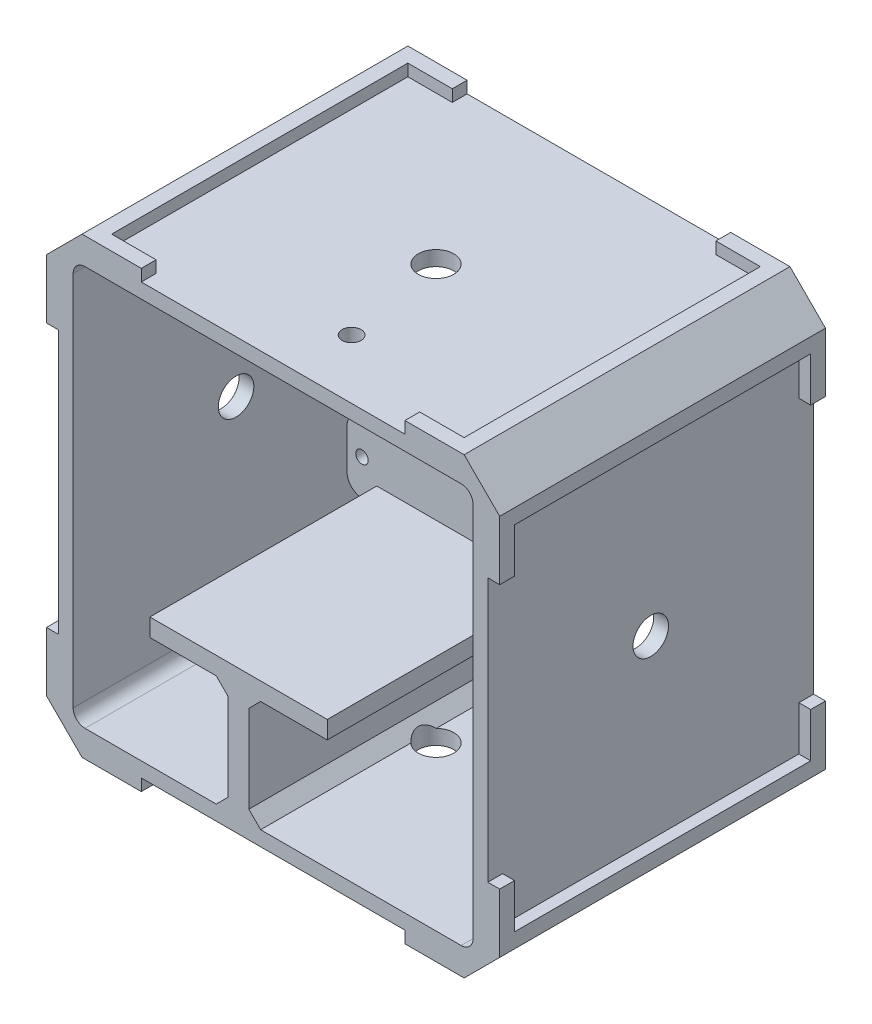
SolidWorks part; units mm, degrees
ref_plane "Front Plane" through (0, 0, 0) normal (0, 0, 1) x (1, 0, 0)
ref_plane "Top Plane" through (0, 0, 0) normal (0, 1, 0) x (1, 0, 0)
ref_plane "Right Plane" through (0, 0, 0) normal (1, 0, 0) x (0, 0, -1)
sketch "Sketch1" plane through (0, 0, 0) normal (0, 0, 1) x (1, 0, 0)
  line L0 (-33.75, -33.75) -> (33.75, -33.75) construction
  line L1 (-31.75, 33.75) -> (31.75, 33.75)
  line L2 (-33.75, 31.75) -> (-33.75, -31.75)
  line L3 (-31.75, -33.75) -> (31.75, -33.75)
  line L4 (33.75, 31.75) -> (33.75, -31.75)
  line L5 (-36.25, 32.25) -> (-36.25, -32.25)
  line L6 (33.75, 33.75) -> (33.75, -33.75) construction
  line L7 (-32.25, -36.25) -> (32.25, -36.25)
  line L8 (36.25, 32.25) -> (36.25, -32.25)
  line L9 (-32.25, 36.25) -> (32.25, 36.25)
  line L10 (-36.25, 36.25) -> (-36.25, -36.25) construction
  line L11 (-36.25, 36.25) -> (36.25, 36.25) construction
  line L12 (-33.75, 33.75) -> (33.75, 33.75) construction
  line L13 (-33.75, 33.75) -> (-33.75, -33.75) construction
  line L14 (-36.25, -36.25) -> (36.25, -36.25) construction
  line L15 (36.25, 36.25) -> (36.25, -36.25) construction
  line L16 (55, 0) -> (-55, 0) construction
  line L17 (0, -55) -> (0, 55) construction
  arc A0 (-36.25, 32.25) -> (-32.25, 36.25) centre (-32.25, 32.25) cw
  arc A1 (-31.75, 33.75) -> (-33.75, 31.75) centre (-31.75, 31.75) ccw
  arc A2 (-33.75, -31.75) -> (-31.75, -33.75) centre (-31.75, -31.75) ccw
  arc A3 (31.75, -33.75) -> (33.75, -31.75) centre (31.75, -31.75) ccw
  arc A4 (31.75, 33.75) -> (33.75, 31.75) centre (31.75, 31.75) cw
  arc A5 (-36.25, -32.25) -> (-32.25, -36.25) centre (-32.25, -32.25) ccw
  arc A6 (32.25, -36.25) -> (36.25, -32.25) centre (32.25, -32.25) ccw
  arc A7 (36.25, 32.25) -> (32.25, 36.25) centre (32.25, 32.25) ccw
  point P36 (-33.75, 0)
  point P39 (0, 33.75)
  dimension "D3" = 4
  dimension "D4" = 2
  dimension "D5" = 2
  dimension "D6" = 4
  dimension "D1" = 67.5
  dimension "D2" = 2.5
extrude "Boss-Extrude1" add sketch "Sketch1" along normal blind 55
sketch "Sketch2" plane through (0, 0, 0) normal (0, 0, 1) x (1, 0, 0)
  line L1 (-33.75, 33.75) -> (33.75, 33.75)
  line L2 (-33.75, 33.75) -> (-33.75, -33.75)
  line L3 (-33.75, -33.75) -> (33.75, -33.75)
  line L4 (33.75, 33.75) -> (33.75, -33.75)
extrude "Boss-Extrude2" add sketch "Sketch2" along normal blind 2.5
sketch "Sketch4" plane through (0, 0, 0) normal (0, 0, -1) x (-1, 0, 0)
  line L0 (-32.25, 36.25) -> (32.25, 36.25) construction
  line L1 (-36.25, -32.25) -> (-36.25, 32.25) construction
  circle A0 centre (-28.75, 28.75) radius 1.65
  dimension "D3" = 3.3
  dimension "D1" = 7.5
  dimension "D2" = 7.5
extrude "Cut-Extrude2" cut sketch "Sketch4" against normal up to next
mirror "Mirror1" about plane through (0, 0, 0) normal (1, 0, 0) of "Cut-Extrude2"
mirror "Mirror2" about plane through (0, 0, 0) normal (0, 1, 0) of "Mirror1"
sketch "Sketch5" plane through (0, 0, 0) normal (1, 0, 0) x (0, 0, -1)
  line L2 (-16.7, 12) -> (-16.7, -12)
  line L3 (-16.7, -12) -> (-60.4, -12)
  line L6 (-13.7, -15) -> (-63.4, -15)
  line L7 (-13.7, 12) -> (-13.7, -15)
  line L9 (-60.4, -12) -> (-63.4, -12)
  line L10 (-63.4, -12) -> (-63.4, -15)
  line L11 (-60.4, 12) -> (-60.4, -12) construction
  line L12 (-63.4, 15) -> (-63.4, -15) construction
  line L13 (0, 39.875) -> (0, -39.875) construction
  line L15 (-16.7, 12) -> (-13.7, 12)
  line L16 (-13.7, 15) -> (-13.7, -15) construction
  line L17 (-13.7, 15) -> (-63.4, 15) construction
  line L18 (-16.7, 12) -> (-60.4, 12) construction
  dimension "D1" = 24
  dimension "D2" = 49.7
  dimension "D4" = 13.7
  dimension "D3" = 3
extrude "Boss-Extrude3" add sketch "Sketch5" along normal blind 14.6 and the other way blind 25.8 separate body
sketch "Sketch6" plane through (0, 0, 63.4) normal (0, 0, 1) x (1, 0, 0)
  line L1 (-25.8, -12) -> (12.1, -12)
  line L2 (-25.8, -12) -> (-25.8, -15)
  line L3 (-25.8, -15) -> (-7.6, -15)
  line L4 (12.1, -12) -> (12.1, -15)
  line L6 (-25.8, -36.25) -> (12.1, -36.25)
  line L7 (-25.8, -36.25) -> (-25.8, -33.75)
  line L8 (-25.8, -33.75) -> (-7.6, -33.75)
  line L9 (12.1, -36.25) -> (12.1, -33.75)
  line L10 (-4.1, -15) -> (12.1, -15)
  line L12 (-7.6, -15) -> (-7.6, -33.75)
  line L14 (-4.1, -15) -> (-4.1, -33.75)
  line L15 (-4.1, -33.75) -> (12.1, -33.75)
  line L16 (-25.8, -12) -> (-25.8, -15) construction
  line L17 (-32.25, -36.25) -> (32.25, -36.25) construction
  dimension "D1" = 3
  dimension "D2" = 2.5
  dimension "D3" = 37.9
  dimension "D4" = 37.9
  dimension "D5" = 3.5
  dimension "D6" = 18.2
  dimension "D7" = 18.2
extrude "Boss-Extrude4" add sketch "Sketch6" against normal up to vertex (49.7 mm away) up to point (14.6, 12, 13.7)
sketch "Sketch7" plane through (0, 0, 63.4) normal (0, 0, 1) x (1, 0, 0)
  line L0 (-25.8, -12) -> (-25.8, -15) construction
  line L1 (-25.8, -13.5) -> (12.1, -13.5)
  line L2 (-25.8, -13.5) -> (-25.8, -36.25)
  line L3 (-25.8, -36.25) -> (12.1, -36.25)
  line L4 (12.1, -13.5) -> (12.1, -36.25)
  line L7 (12.1, -36.25) -> (12.1, -33.75) construction
extrude "Cut-Extrude3" cut sketch "Sketch7" against normal blind 8.4
ref_plane "Plane1" through (-11.1, 0, 0) normal (-1, 0, 0) x (0, 0, 1)
sketch "Sketch10" [suppressed] plane through (-36.25, 0, 0) normal (-1, 0, 0) x (0, 0, 1)
  circle A0 centre (22.3967, 9) radius 1.5
  circle A1 centre (22.3967, -9) radius 1.5
  dimension "D1" = 3
  dimension "D2" = 3
extrude "Cut-Extrude4" [suppressed] cut sketch "Sketch10" against normal through all
sketch "Sketch12" plane through (0, 36.25, 0) normal (0, 1, 0) x (1, 0, 0)
  line L0 (-32.25, -55) -> (-32.25, 0) construction
  line L1 (32.25, -55) -> (29.75, -55)
  line L2 (32.25, -55) -> (32.25, -45)
  line L3 (32.25, -45) -> (29.75, -45)
  line L4 (29.75, -52.5) -> (29.75, -45)
  line L5 (32.25, -55) -> (22.25, -55)
  line L6 (32.25, -55) -> (32.25, -52.5)
  line L7 (29.75, -52.5) -> (22.25, -52.5)
  line L8 (22.25, -55) -> (22.25, -52.5)
  line L10 (-32.25, 0) -> (-32.25, -10)
  line L11 (-32.25, -10) -> (-29.75, -10)
  line L12 (-29.75, -2.5) -> (-29.75, -10)
  line L13 (-32.25, 0) -> (-22.25, 0)
  line L15 (-29.75, -2.5) -> (-22.25, -2.5)
  line L16 (-22.25, 0) -> (-22.25, -2.5)
  line M6 (-32.25, -55) -> (32.25, -55)
  line M7 (32.25, -55) -> (32.25, 0)
  dimension "D1" = 2.5
  dimension "D2" = 10
  dimension "D3" = 2.5
  dimension "D4" = 10
  dimension "D5" = 2.5
extrude "Boss-Extrude7" add sketch "Sketch12" along normal blind 2 contours L8 L2 L3 L4 L7 M6 M7 | L10 L11 L12 L15 L16 L13 region at (31, 36.25, 54.8586)
sketch "Sketch13" plane through (0, 0, 0) normal (0, 0, -1) x (-1, 0, 0)
  line L3 (-33.75, 21.25) -> (-25.25, 21.25)
  line L4 (-21.25, 33.75) -> (-21.25, 25.25)
  line L6 (0, 34.87) -> (0, -34.87) construction
  line L8 (21.25, 33.75) -> (21.25, 25.25)
  line L9 (33.75, 21.25) -> (25.25, 21.25)
  line L12 (34.87, 0) -> (-34.87, 0) construction
  line L17 (33.75, -21.25) -> (25.25, -21.25)
  line L18 (21.25, -33.75) -> (21.25, -25.25)
  line L19 (-21.25, -33.75) -> (-21.25, -25.25)
  line L20 (-33.75, -21.25) -> (-25.25, -21.25)
  line L27 (-33.75, 21.25) -> (-33.75, -21.25)
  line L29 (33.75, 21.25) -> (33.75, -21.25)
  line L34 (-21.25, 33.75) -> (21.25, 33.75)
  line L36 (-21.25, -33.75) -> (21.25, -33.75)
  arc A2 (-25.25, 21.25) -> (-21.25, 25.25) centre (-25.25, 25.25) ccw
  arc A4 (25.25, 21.25) -> (21.25, 25.25) centre (25.25, 25.25) cw
  arc A7 (25.25, -21.25) -> (21.25, -25.25) centre (25.25, -25.25) ccw
  arc A8 (-25.25, -21.25) -> (-21.25, -25.25) centre (-25.25, -25.25) cw
  dimension "D3" = 4
extrude "Cut-Extrude6" cut sketch "Sketch13" against normal up to next and the other way through all
sketch "Sketch15" plane through (0, 36.25, 0) normal (0, 1, 0) x (1, 0, 0)
  line L0 (22.25, -55) -> (-32.25, -55) construction
  line L1 (33.75, -55) -> (33.75, -2.5) construction
  circle A0 centre (3.25, -45) radius 1.6
  dimension "D1" = 3.2
  dimension "D2" = 10
  dimension "D3" = 30.5
extrude "Cut-Extrude8" cut sketch "Sketch15" against normal up to surface (2.5 mm away) and the other way through all up to face at (0, 33.75, 15)
sketch "Sketch16" plane through (-33.75, 0, 0) normal (1, 0, 0) x (0, 0, -1)
  line L0 (-55, 36.25) -> (-10, 36.25) construction
  line L2 (-16, 28.7) -> (-16, 30.35)
  line L7 (-16, 30.35) -> (-8.5, 30.35)
  line L9 (-16, 28.7) -> (-8.5, 28.7)
  line L10 (-8.5, 30.35) -> (-8.5, 28.7)
  line L12 (0, -32.25) -> (0, 32.25) construction
  dimension "D1" = 7.5
  dimension "D2" = 7.55
  dimension "D3" = 16
  dimension "D4" = 1.65
extrude "Boss-Extrude8" add sketch "Sketch16" along normal blind 7
sketch "Sketch17" plane through (0, 0, 13.7) normal (0, 0, -1) x (-1, 0, 0)
  line L0 (-14.6, -15) -> (-14.6, 12) construction
  line L2 (25.8, -15) -> (25.8, 12) construction
  line L3 (25.8, 12) -> (-14.6, 12) construction
  circle A0 centre (-12.1, 9) radius 1.05
  circle A1 centre (-12.1, -9) radius 1.05
  circle A2 centre (23.3, -9) radius 1.05
  dimension "D1" = 2.1
  dimension "D2" = 2.5
  dimension "D3" = 3
  dimension "D4" = 2.5
  dimension "D6" = 18
extrude "Cut-Extrude9" cut sketch "Sketch17" against normal up to next
sketch "Sketch19" plane through (0, 36.25, 0) normal (0, 1, 0) x (1, 0, 0)
  line L0 (32.25, -55) -> (-32.25, 0) construction
  line L1 (-32.25, 0) -> (-22.25, 0) construction
  line L2 (32.25, 0) -> (-32.25, -55) construction
  line L3 (32.25, -45) -> (32.25, 0) construction
  line L4 (32.25, 0) -> (-22.25, 0) construction
  line L5 (-32.25, 0) -> (-32.25, -10) construction
  line L6 (-32.25, 0) -> (-32.25, -10) construction
  circle A0 centre (0, -27.5) radius 3
  dimension "D1" = 6
extrude "Cut-Extrude10" cut sketch "Sketch19" against normal blind 2.5
sketch "Sketch20" plane through (36.25, 0, -36.25) normal (-1, 0, 0) x (0, 0, 1)
  line L0 (36.25, -32.25) -> (36.25, 32.25) construction
  line L1 (36.25, -32.25) -> (36.25, -22.25)
  line L2 (36.25, -32.25) -> (46.25, -32.25)
  line L3 (46.25, -32.25) -> (46.25, -29.75)
  line L4 (38.75, -29.75) -> (46.25, -29.75)
  line L5 (36.25, -32.25) -> (36.25, -22.25)
  line L7 (38.75, -29.75) -> (38.75, -22.25)
  line L8 (36.25, -22.25) -> (38.75, -22.25)
  line L10 (91.25, 32.25) -> (81.25, 32.25)
  line L11 (81.25, 32.25) -> (81.25, 29.75)
  line L12 (88.75, 29.75) -> (81.25, 29.75)
  line L13 (91.25, 32.25) -> (91.25, 22.25)
  line L15 (88.75, 29.75) -> (88.75, 22.25)
  line L16 (91.25, 22.25) -> (88.75, 22.25)
  line M25 (36.25, -32.25) -> (36.25, 32.25)
  line M26 (36.25, 32.25) -> (91.25, 32.25)
  line M27 (91.25, 32.25) -> (91.25, -32.25)
  line M28 (91.25, -32.25) -> (36.25, -32.25)
  dimension "D1" = 2.5
  dimension "D2" = 10
  dimension "D3" = 2.5
  dimension "D4" = 10
  dimension "D5" = 2.5
  dimension "D6" = 55
  dimension "D7" = 64.5
  dimension "D8" = 10
  dimension "D9" = 7.5
  dimension "D10" = 7.5
extrude "Boss-Extrude9" add sketch "Sketch20" against normal blind 2 contours L16 L15 L12 L11 M27 M26 | L8 L7 L4 L3 M25 M28 region at (36.25, -27.25, 0.1414) region at (36.25, 32.1086, 50)
ref_axis "Axis1" through (0, 0, 67.62) along (0, 0, -1)
pattern_circular "CirPattern1" count 4 every 90 about axis through (0, 0, 67.62) along (0, 0, -1) of "Boss-Extrude7", "Cut-Extrude10"
pattern_circular "CirPattern2" count 4 every 90 about axis through (0, 0, 67.62) along (0, 0, -1) of "Boss-Extrude9"
sketch "Sketch22" plane through (0, 0, 55) normal (0, 0, 1) x (1, 0, 0)
  line L0 (-38.25, 32.25) -> (-32.25, 38.25)
  line L1 (-32.25, 38.25) -> (-29.75, 38.25)
  line L8 (-29.75, 38.25) -> (-29.75, 33.75)
  line L13 (-38.25, 29.75) -> (-33.75, 29.75)
  line L20 (-38.25, 29.75) -> (-38.25, 32.25)
  line L24 (-32.25, 38.25) -> (-22.25, 38.25) construction
  line L26 (-33.75, 31.75) -> (-33.75, -31.75) construction
  line L27 (-38.25, 22.25) -> (-38.25, 32.25) construction
  line L28 (0, -34.87) -> (0, 34.87) construction
  line L29 (33.75, 33.75) -> (33.75, 29.75)
  line L30 (33.75, 33.75) -> (29.75, 33.75)
  line L31 (38.25, 29.75) -> (38.25, 32.25)
  line L32 (38.25, 29.75) -> (33.75, 29.75)
  line L33 (-33.75, 33.75) -> (-29.75, 33.75)
  line L34 (-33.75, 33.75) -> (-33.75, 29.75)
  line L37 (29.75, 38.25) -> (29.75, 33.75)
  line L38 (32.25, 38.25) -> (29.75, 38.25)
  line L39 (38.25, 32.25) -> (32.25, 38.25)
  line L40 (34.87, 0) -> (-34.87, 0) construction
  line L41 (38.25, -32.25) -> (32.25, -38.25)
  line L42 (32.25, -38.25) -> (29.75, -38.25)
  line L43 (29.75, -38.25) -> (29.75, -33.75)
  line L44 (-33.75, -33.75) -> (-33.75, -29.75)
  line L45 (-33.75, -33.75) -> (-29.75, -33.75)
  line L46 (38.25, -29.75) -> (33.75, -29.75)
  line L47 (38.25, -29.75) -> (38.25, -32.25)
  line L48 (33.75, -33.75) -> (29.75, -33.75)
  line L49 (33.75, -33.75) -> (33.75, -29.75)
  line L50 (-38.25, -29.75) -> (-38.25, -32.25)
  line L51 (-38.25, -29.75) -> (-33.75, -29.75)
  line L52 (-29.75, -38.25) -> (-29.75, -33.75)
  line L53 (-32.25, -38.25) -> (-29.75, -38.25)
  line L54 (-38.25, -32.25) -> (-32.25, -38.25)
  dimension "D1" = 2.5
  dimension "D2" = 2.5
extrude "Boss-Extrude12" add sketch "Sketch22" against normal through all
sketch "Sketch23" plane through (0, 0, 13.7) normal (0, 0, -1) x (-1, 0, 0)
  line L0 (25.8, 12) -> (-14.6, 12) construction
  line L1 (19.3, 12) -> (25.8, 12)
  line L2 (19.3, 12) -> (19.3, -4)
  line L3 (19.3, -4) -> (25.8, -4)
  line L4 (25.8, 12) -> (25.8, -4)
  line L5 (25.8, -15) -> (25.8, 12) construction
  circle A0 centre (23.3, -9) radius 1.05 construction
  dimension "D1" = 5
  dimension "D2" = 6.5
extrude "Cut-Extrude12" cut sketch "Sketch23" against normal up to next
fillet "Fillet2" radius 1.5 1 edges at (14.6, 12, 15.2)
chamfer "Chamfer1" distance 0.75 angle 45 3 edges at (-26.75, 30.35, 12.25) (-30.25, 30.35, 16) (-33.75, 28.7, 12.25)
sketch "Sketch25" plane through (0, -12, 0) normal (0, 1, 0) x (1, 0, 0)
  line L0 (-25.8, -16.7) -> (14.6, -16.7) construction
  line L1 (14.6, -63.4) -> (11.6, -63.4)
  line L2 (14.6, -63.4) -> (14.6, -28.4)
  line L3 (14.6, -28.4) -> (11.6, -28.4)
  line L4 (11.6, -63.4) -> (11.6, -28.4)
  line L5 (-25.8, -63.4) -> (-20.8, -63.4)
  line L6 (-25.8, -63.4) -> (-25.8, -16.7)
  line L7 (-25.8, -16.7) -> (-20.8, -16.7)
  line L8 (-20.8, -63.4) -> (-20.8, -16.7)
  dimension "D1" = 3
  dimension "D2" = 35
  dimension "D3" = 5
extrude "Cut-Extrude13" cut sketch "Sketch25" against normal up to next
fillet "Fillet3" radius 1.5 3 edges at (-19.3, 12, 15.2) (-19.3, -4, 15.2) (-25.8, -4, 15.2)
sketch "Sketch26" plane through (11.6, 0, 0) normal (1, 0, 0) x (0, 0, -1)
  line L0 (-55, -22.25) -> (-55, 22.25) construction
  line L1 (-67.544, -8.4561) -> (-55, -8.4561)
  line L2 (-67.544, -8.4561) -> (-67.544, -18.0422)
  line L3 (-67.544, -18.0422) -> (-55, -18.0422)
  line L4 (-55, -8.4561) -> (-55, -18.0422)
extrude "Cut-Extrude14" cut sketch "Sketch26" against normal through all
sketch "Sketch27" plane through (-33.75, 0, 0) normal (1, 0, 0) x (0, 0, -1)
  line L0 (-55, 31.75) -> (-2.5, 31.75) construction
  line L1 (-15.25, 30.35) -> (-8.5, 30.35)
  line L2 (-15.25, 30.35) -> (-15.25, 31.75)
  line L3 (-15.25, 31.75) -> (-8.5, 31.75)
  line L4 (-8.5, 30.35) -> (-8.5, 31.75)
  line L5 (-8.5, 27.95) -> (-8.5, 30.35) construction
extrude "Boss-Extrude14" add sketch "Sketch27" along normal blind 1.25
chamfer "Chamfer2" distance 2 angle 45 4 edges at (-4.1, -33.75, 34.35) (-7.6, -33.75, 34.35) (-7.6, -15, 34.35) (-4.1, -15, 34.35)
sketch "Sketch28" plane through (0, -12, 0) normal (0, 1, 0) x (1, 0, 0)
  line L0 (-20.8, -16.7) -> (14.6, -16.7) construction
  line L1 (9.15, -16.7) -> (16.7741, -16.7)
  line L2 (9.15, -16.7) -> (9.15, -63.0731)
  line L3 (9.15, -63.0731) -> (16.7741, -63.0731)
  line L4 (16.7741, -16.7) -> (16.7741, -63.0731)
  line L5 (33.75, -55) -> (33.75, -2.5) construction
  dimension "D1" = 24.6
extrude "Cut-Extrude15" cut sketch "Sketch28" against normal up to next
fillet "Fillet5" radius 2.5 2 edges at (14.6, -15, 15.2) (-25.8, -15, 15.2)
